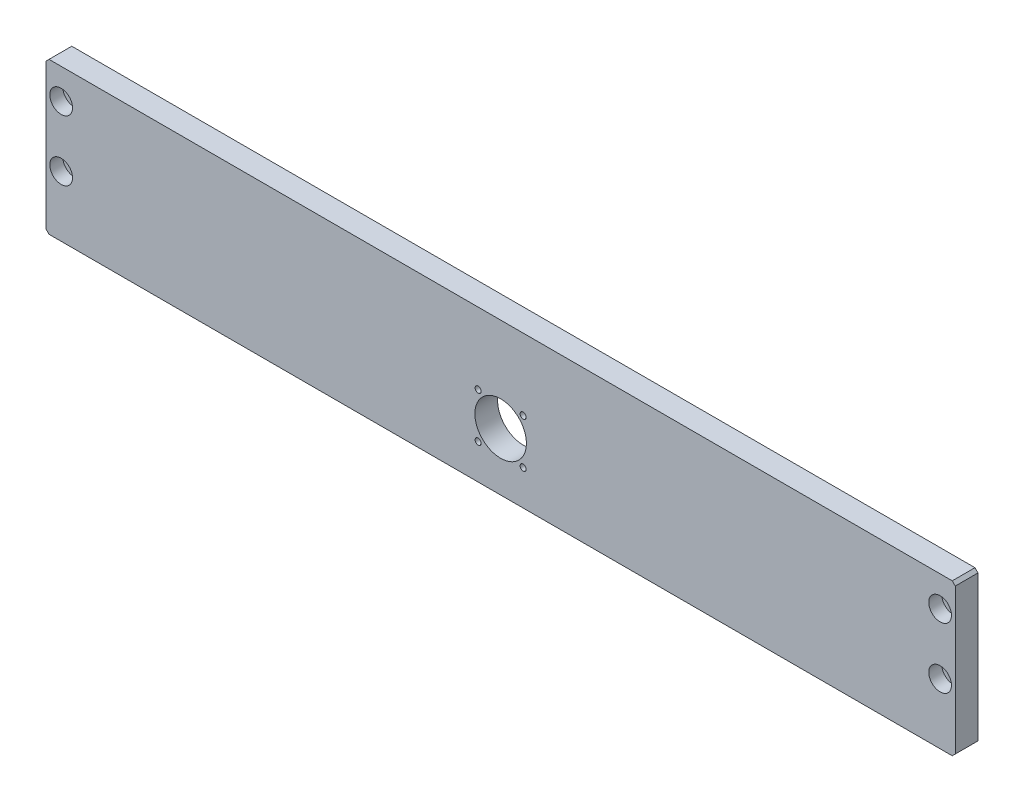
SolidWorks part; units mm, degrees
ref_plane "Piano frontale" through (0, 0, 0) normal (0, 0, 1) x (1, 0, 0)
ref_plane "Piano superiore" through (0, 0, 0) normal (0, 1, 0) x (1, 0, 0)
ref_plane "Piano destro" through (0, 0, 0) normal (1, 0, 0) x (0, 0, -1)
sketch "Schizzo1" plane through (0, 0, 0) normal (0, 0, 1) x (1, 0, 0)
  line L0 (300, 100) -> (300, 0) construction
  line L1 (2, 0) -> (598, 0)
  line L2 (0, 2) -> (0, 98)
  line L3 (2, 100) -> (598, 100)
  line L4 (600, 2) -> (600, 98)
  line L5 (300, 38) -> (270.4474, 67.5526) construction
  line L7 (300, 38) -> (318.5099, 38) construction
  line L9 (211.2881, 38) -> (400.934, 38) construction
  line L21 (0, 98) -> (2, 100)
  line L22 (2, 0) -> (0, 2)
  line L23 (598, 0) -> (600, 2)
  line L24 (598, 100) -> (600, 98)
  circle A0 centre (300, 38) radius 17
  circle A1 centre (300, 38) radius 21 construction
  circle A2 centre (314.8492, 52.8492) radius 2
  circle A4 centre (314.8492, 23.1508) radius 2
  circle A5 centre (285.1508, 23.1508) radius 2
  circle A13 centre (285.1508, 52.8492) radius 2
  point P0 (0, 0)
  point P1 (600, 100)
  point P2 (0, 100)
  point P3 (600, 0)
  point P13 (285.1508, 52.8492)
  point P14 (314.8492, 52.8492)
  point P15 (285.1508, 23.1508)
  point P17 (314.8492, 23.1508)
  dimension "D4" = 34
  dimension "D17" = 4
  dimension "D8" = 42
  dimension "D1" = 100
  dimension "D2" = 600
  dimension "D3" = 38
  dimension "D5" = 45
extrude "Estrusione-Estrusione1" add sketch "Schizzo1" against normal blind 15
sketch "Sketch1" plane through (0, 0, 0) normal (0, -1, 0) x (1, 0, 0)
  line L0 (2, -7.5) -> (598, -7.5) construction
  line L1 (2, -15) -> (2, 0) construction
  line L2 (598, -15) -> (598, 0) construction
  line L3 (300, 0) -> (300, -15) construction
  line L4 (2, 0) -> (598, 0) construction
  line L5 (2, -15) -> (598, -15) construction
  line L6 (0, -15) -> (0, 0) construction
  point P12 (30, -7.5)
  point P15 (570, -7.5)
  dimension "D1" = 30
hole_wizard "M8 Tapped Hole1" positions "3DSketch2" profile "Sketch2" tap size "M8" standard "ISO"
sketch3d "3DSketch2"
  point P0 (30, 0, -7.5)
  point P3 (570, 0, -7.5)
sketch "Sketch2" plane through (30, 0, -7.5) normal (1, 0, 0) x (0, 0, -1)
  line L0 (0, 0) -> (0, 25.7929)
  line L1 (0, 25.7929) -> (3.4, 23.75)
  line L2 (3.4, 23.75) -> (3.4, 0)
  line L5 (3.4, 0) -> (0, 0)
  line L10 (0, 25.7929) -> (-3.4, 23.75) construction
  line L11 (0, -6.35) -> (0, 107.95) construction
  dimension "Tap Drill Dia." = 6.8
  dimension "Tap Drill Depth" = 23.75
  dimension "Drill Angle" = 118
sketch "Sketch3" plane through (0, 0, 0) normal (0, 0, 1) x (1, 0, 0)
  line L0 (10, 100) -> (10, 0) construction
  line L1 (0, 100) -> (600, 100) construction
  line L2 (2, 0) -> (598, 0) construction
  line L3 (0, 98) -> (0, 2) construction
  line L4 (300, 100) -> (300, 0) construction
  line L5 (598, 100) -> (2, 100) construction
  line L6 (2, 0) -> (598, 0) construction
  point P9 (10, 80)
  point P10 (10, 40)
  point P17 (590, 40)
  point P18 (590, 80)
  dimension "D1" = 10
  dimension "D2" = 20
  dimension "D3" = 40
hole_wizard "CBORE for M8 Hex Socket Head Cap Screw1" positions "3DSketch3" profile "Sketch4" counterbore size "M8" standard "ISO"
sketch3d "3DSketch3"
  point P0 (10, 80, 0)
  point P3 (10, 40, 0)
  point P6 (590, 80, 0)
  point P11 (590, 40, 0)
sketch "Sketch4" plane through (10, 80, 0) normal (1, 0, 0) x (0, -1, 0)
  line L0 (0, 0) -> (0, 23.75)
  line L1 (0, 23.75) -> (4.5, 23.75)
  line L2 (4.5, 23.75) -> (4.5, 8.6)
  line L3 (4.5, 8.6) -> (7.5, 8.6)
  line L4 (7.5, 8.6) -> (7.5, 0)
  line L5 (7.5, 0) -> (0, 0)
  line L10 (0, 23.75) -> (-4.5, 23.75) construction
  line L11 (0, -6.35) -> (0, 107.95) construction
  dimension "Hole Dia." = 9
  dimension "Hole Depth" = 23.75
  dimension "C'Bore Dia." = 15
  dimension "C'Bore Depth" = 8.6
  dimension "Drill Angle" = 180
